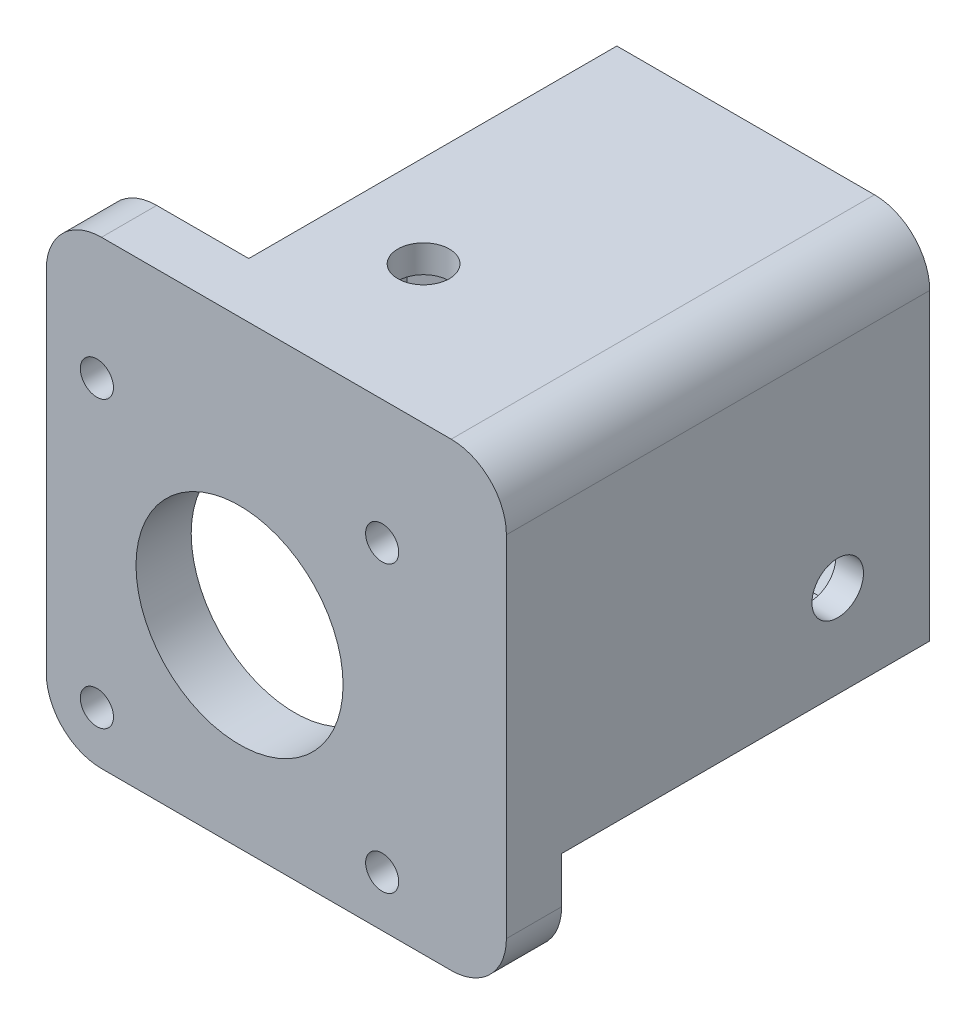
SolidWorks part; units mm, degrees
ref_plane "Front Plane" through (0, 0, 0) normal (0, 0, 1) x (1, 0, 0)
ref_plane "Top Plane" through (0, 0, 0) normal (0, 1, 0) x (1, 0, 0)
ref_plane "Right Plane" through (0, 0, 0) normal (1, 0, 0) x (0, 0, -1)
sketch "Sketch1" plane through (0, 0, 0) normal (0, 0, 1) x (1, 0, 0)
  line L1 (-50, 50) -> (0, 50)
  line L2 (-50, 50) -> (-50, 0)
  line L3 (-50, 0) -> (0, 0)
  line L4 (0, 50) -> (0, 0)
  dimension "D1" = 50
extrude "Boss-Extrude1" add sketch "Sketch1" against normal blind 6
sketch "Sketch2" plane through (0, 0, -6) normal (0, 0, -1) x (-1, 0, 0)
  line L0 (0, 0) -> (0, 50) construction
  line L1 (0, 39) -> (6, 39)
  line L2 (0, 39) -> (0, 0)
  line L3 (0, 0) -> (6, 0)
  line L4 (6, 39) -> (6, 6)
  line L5 (50, 0) -> (0, 0) construction
  line L7 (6, 6) -> (34, 6)
  line L9 (6, 0) -> (34, 0)
  line L10 (34, 6) -> (34, 0)
  dimension "D1" = 39
  dimension "D2" = 6
  dimension "D3" = 28
extrude "Boss-Extrude2" add sketch "Sketch2" along normal blind 40
sketch "Sketch3" plane through (0, 0, 0) normal (0, 0, 1) x (1, 0, 0)
  line L0 (0, 50) -> (-50, 50) construction
  line L1 (-50, 50) -> (-50, 0) construction
  line L2 (-50, 29) -> (0, 29) construction
  line L3 (0, 0) -> (0, 50) construction
  line L4 (-29, 50) -> (-29, 0) construction
  line L5 (-50, 0) -> (0, 0) construction
  point P0 (-44.5, 44.5)
  point P4 (-29, 29)
  point P9 (-13.5, 44.5)
  point P19 (-44.5, 13.5)
  point P20 (-13.5, 13.5)
  dimension "D1" = 5.5
  dimension "D2" = 5.5
  dimension "D3" = 21
  dimension "D4" = 21
hole_wizard "Ø3.6mm Dowel Hole1" positions "Sketch4" profile "Sketch5" hole size "Ø4.0" standard "ANSI Metric" end condition through all
sketch "Sketch4" plane through (0, 0, 0) normal (0, 0, 1) x (1, 0, 0)
  point P0 (-44.5, 44.5)
  point P3 (-13.5, 44.5)
  point P6 (-13.5, 13.5)
  point P9 (-44.5, 13.5)
sketch "Sketch5" plane through (-44.5, 44.5, 0) normal (1, 0, 0) x (0, -1, 0)
  line L0 (0, 0) -> (0, 46)
  line L1 (0, 46) -> (1.8, 46)
  line L2 (1.8, 46) -> (1.8, 0)
  line L5 (1.8, 0) -> (0, 0)
  line L11 (0, -6.35) -> (0, 107.95) construction
  dimension "Thru Hole Dia." = 3.6
  dimension "Thru Hole Depth" = 46
hole_wizard "Ø22.5mm Dowel Hole1" positions "Sketch6" profile "Sketch7" hole size "Ø20.0" standard "ANSI Metric" end condition through all
sketch "Sketch6" plane through (0, 0, 0) normal (0, 0, 1) x (1, 0, 0)
  point P0 (-29, 29)
sketch "Sketch7" plane through (-29, 29, 0) normal (1, 0, 0) x (0, -1, 0)
  line L0 (0, 0) -> (0, 46)
  line L1 (0, 46) -> (11.25, 46)
  line L2 (11.25, 46) -> (11.25, 0)
  line L5 (11.25, 0) -> (0, 0)
  line L11 (0, -6.35) -> (0, 107.95) construction
  dimension "Thru Hole Dia." = 22.5
  dimension "Thru Hole Depth" = 46
hole_wizard "Ø5.6mm Dowel Hole1" positions "3DSketch1" profile "Sketch8" hole size "Ø5.0" standard "ANSI Metric" end condition through all
sketch3d "3DSketch1"
  line L0 (0, 39, -46) -> (0, 39, -6) construction
  line L1 (0, 39, -46) -> (0, 0, -46) construction
  point P0 (0, 29, -36)
  dimension "D1" = 10
  dimension "D2" = 10
sketch "Sketch8" plane through (0, 29, -36) normal (0, 1, 0) x (0, 0, -1)
  line L0 (0, 0) -> (0, 50)
  line L1 (0, 50) -> (2.8, 50)
  line L2 (2.8, 50) -> (2.8, 0)
  line L5 (2.8, 0) -> (0, 0)
  line L11 (0, -6.35) -> (0, 107.95) construction
  dimension "Thru Hole Dia." = 5.6
  dimension "Thru Hole Depth" = 50
hole_wizard "Ø5.6mm Dowel Hole2" positions "Sketch9" profile "Sketch10" hole size "Ø5.0" standard "ANSI Metric" end condition through all
sketch "Sketch9" plane through (0, 0, 0) normal (0, -1, 0) x (-1, 0, 0)
  line L0 (34, 46) -> (34, 6) construction
  line L1 (50, 0) -> (0, 0) construction
  point P0 (24, 15)
  dimension "D1" = 10
  dimension "D2" = 15
sketch "Sketch10" plane through (-24, 0, -15) normal (1, 0, 0) x (0, 0, -1)
  line L0 (0, 0) -> (0, 50)
  line L1 (0, 50) -> (2.8, 50)
  line L2 (2.8, 50) -> (2.8, 0)
  line L5 (2.8, 0) -> (0, 0)
  line L11 (0, -6.35) -> (0, 107.95) construction
  dimension "Thru Hole Dia." = 5.6
  dimension "Thru Hole Depth" = 50
sketch "Sketch12" plane through (0, 6, 0) normal (0, 1, 0) x (1, 0, 0)
  line L1 (-28.2, 12.5751) -> (-24, 10.1503)
  line L2 (-24, 10.1503) -> (-19.8, 12.5751)
  line L3 (-19.8, 12.5751) -> (-19.8, 17.4249)
  line L4 (-19.8, 17.4249) -> (-24, 19.8497)
  line L5 (-24, 19.8497) -> (-28.2, 17.4249)
  line L6 (-28.2, 17.4249) -> (-28.2, 12.5751)
  circle A0 centre (-24, 15) radius 4.2 construction
  dimension "D1" = 8.4
sketch "Sketch13" plane through (-6, 0, 0) normal (-1, 0, 0) x (0, 0, 1)
  line L1 (-40.8497, 29) -> (-38.4249, 24.8)
  line L2 (-38.4249, 24.8) -> (-33.5751, 24.8)
  line L3 (-33.5751, 24.8) -> (-31.1503, 29)
  line L4 (-31.1503, 29) -> (-33.5751, 33.2)
  line L5 (-33.5751, 33.2) -> (-38.4249, 33.2)
  line L6 (-38.4249, 33.2) -> (-40.8497, 29)
  circle A0 centre (-36, 29) radius 4.2 construction
  dimension "D1" = 8.4
extrude "Cut-Extrude1" cut sketch "Sketch12" against normal blind 3
extrude "Cut-Extrude2" cut sketch "Sketch13" against normal blind 3
fillet "Fillet1" radius 6 4 edges at (-50, 0, -3) (-50, 50, -3) (0, 0, -23) (0, 50, -3)
mirror "Mirror2" about plane through (0, 0, 0) normal (0, 1, 0) of "Fillet1", "Cut-Extrude2", "Cut-Extrude1", "Ø5.6mm Dowel Hole2", "Ø5.6mm Dowel Hole1", "Ø22.5mm Dowel Hole1", "Ø3.6mm Dowel Hole1", "Boss-Extrude2", "Boss-Extrude1"
split "Split1" trim tools "Top Plane" bodies to split 109 resulting bodies 111
equation "\"D4@Sketch3\"=\"D3@Sketch3\""
equation "\"D2@Sketch3\"=\"D1@Sketch3\""
